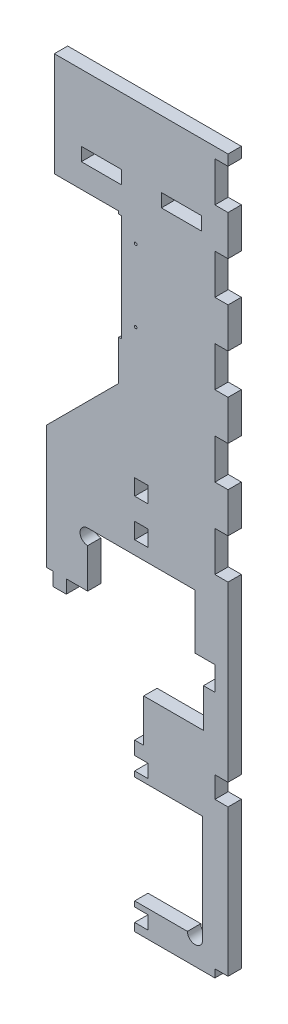
SolidWorks part; units mm, degrees
material "Balsa"
ref_plane "Plan de face" through (0, 0, 0) normal (0, 0, 1) x (1, 0, 0)
ref_plane "Plan de dessus" through (0, 0, 0) normal (0, 1, 0) x (1, 0, 0)
ref_plane "Plan de droite" through (0, 0, 0) normal (1, 0, 0) x (0, 0, -1)
sketch "Esquisse1" plane through (0, 0, 0) normal (0, 0, 1) x (1, 0, 0)
  line L0 (65.1211, 0) -> (30.1224, 0)
  line L2 (65.1211, 0) -> (65.1211, 270)
  line L3 (65.1211, 270) -> (0, 270)
  line L4 (0, 270) -> (0, 231)
  line L5 (0, 231) -> (24.1211, 231)
  line L6 (-2.8789, 101.7504) -> (12.493, 101.7504)
  line L7 (12.493, 101.7504) -> (12.493, 122.247)
  line L8 (12.493, 122.247) -> (52.693, 122.247)
  line L9 (52.693, 122.247) -> (52.693, 101.7504)
  line L10 (52.693, 101.7504) -> (55.9116, 101.7504)
  line L11 (1.3186, 101.7504) -> (30.1224, 101.7504) construction
  line L12 (55.9116, 101.7504) -> (55.9116, 78.2407)
  line L13 (55.9116, 78.2407) -> (33.5123, 78.2407)
  line L14 (33.5123, 78.2407) -> (33.5123, 62.2)
  line L15 (33.5123, 62.2) -> (30.1224, 62.2)
  line L16 (30.1224, 62.2) -> (30.1224, 57.2)
  line L17 (30.1224, 50.2) -> (55.6176, 50.2)
  line L18 (30.1224, 57.2) -> (35.1224, 57.2)
  line L19 (24.1211, 231) -> (24.1211, 175)
  line L20 (35.1224, 57.2) -> (35.1224, 52.2)
  line L21 (24.1211, 175) -> (-2.8789, 148)
  line L22 (-2.8789, 148) -> (-2.8789, 101.7504)
  line L23 (35.1224, 52.2) -> (30.1224, 52.2)
  line L24 (30.1224, 52.2) -> (30.1224, 50.2)
  line L25 (30.1224, 0) -> (30.1224, 3)
  line L26 (30.1224, 3) -> (35.1224, 3)
  line L27 (35.1224, 3) -> (35.1224, 8)
  line L30 (35.1224, 8) -> (30.1224, 8)
  line L31 (30.1224, 8) -> (30.1224, 10)
  line L32 (30.1224, 10) -> (55.6176, 10)
  line L33 (55.6176, 10) -> (55.6176, 50.2)
  dimension "D1" = 270
  dimension "D2" = 65.1211
  dimension "D3" = 40.2
  dimension "D4" = 2
  dimension "D5" = 20.4965
  dimension "D6" = 40.2
  dimension "D7" = 56
  dimension "D8" = 39
  dimension "D9" = 12.4281
  dimension "D10" = 25.4952
  dimension "D11" = 5
  dimension "D12" = 5
  dimension "D13" = 5
  dimension "D14" = 2
  dimension "D15" = 5
  dimension "D16" = 5
  dimension "D17" = 25.4952
  dimension "D18" = 135
  dimension "D19" = 41
  dimension "D20" = 68
extrude "Boss.-Extru.1" add sketch "Esquisse1" against normal blind 5
sketch "Esquisse2" plane through (0, 0, 0) normal (0, 0, 1) x (1, 0, 0)
  line L0 (52.693, 101.7504) -> (55.9116, 101.7504) construction
  line L1 (35.1224, 147.4016) -> (30.1224, 147.4016)
  line L2 (12.493, 122.247) -> (52.693, 122.247) construction
  line L3 (12.493, 101.7504) -> (12.493, 122.247) construction
  line L4 (35.1224, 147.4016) -> (35.1224, 141.4016)
  line L5 (35.1224, 141.4016) -> (30.1224, 141.4016)
  line L6 (30.1224, 147.4016) -> (30.1224, 141.4016)
  line L7 (35.1224, 133.247) -> (30.1224, 133.247)
  line L8 (35.1224, 133.247) -> (35.1224, 127.247)
  line L9 (35.1224, 127.247) -> (30.1224, 127.247)
  line L10 (30.1224, 133.247) -> (30.1224, 127.247)
  line L11 (55.9116, 101.7504) -> (60.186, 101.7504)
  line L12 (55.9116, 101.7504) -> (55.9116, 92.7704)
  line L13 (55.9116, 92.7704) -> (60.186, 92.7704)
  line L14 (60.186, 101.7504) -> (60.186, 92.7704)
  line L15 (52.693, 122.247) -> (52.693, 101.7504) construction
  line L16 (65.1211, 0) -> (65.1211, 270) construction
  line L17 (65.1211, 0) -> (60.2011, 0)
  line L18 (65.1211, 0) -> (65.1211, 3)
  line L19 (65.1211, 3) -> (60.2011, 3)
  line L20 (60.2011, 0) -> (60.2011, 3)
  line L21 (30.1224, 0) -> (65.1211, 0) construction
  line L22 (65.1211, 0) -> (65.1211, 270) construction
  line L23 (65.1211, 58) -> (60.2011, 58)
  line L24 (65.1211, 58) -> (65.1211, 66)
  line L25 (65.1211, 66) -> (60.2011, 66)
  line L26 (60.2011, 58) -> (60.2011, 66)
  line L27 (30.1224, 0) -> (65.1211, 0) construction
  line L28 (65.1211, 161) -> (60.2011, 161)
  line L29 (65.1211, 131) -> (60.2011, 131)
  line L30 (65.1211, 131) -> (65.1211, 146)
  line L31 (65.1211, 146) -> (60.2011, 146)
  line L32 (60.2011, 131) -> (60.2011, 146)
  line L33 (65.1211, 161) -> (65.1211, 176)
  line L34 (65.1211, 176) -> (60.2011, 176)
  line L35 (60.2011, 161) -> (60.2011, 176)
  line L36 (65.1211, 191) -> (60.2011, 191)
  line L37 (65.1211, 191) -> (65.1211, 206)
  line L38 (65.1211, 206) -> (60.2011, 206)
  line L39 (60.2011, 191) -> (60.2011, 206)
  line L40 (65.1211, 221) -> (60.2011, 221)
  line L41 (65.1211, 221) -> (65.1211, 236)
  line L42 (65.1211, 236) -> (60.2011, 236)
  line L43 (60.2011, 221) -> (60.2011, 236)
  line L44 (65.1211, 251) -> (60.2011, 251)
  line L45 (65.1211, 251) -> (65.1211, 266)
  line L46 (65.1211, 266) -> (60.2011, 266)
  line L47 (60.2011, 251) -> (60.2011, 266)
  line L48 (55.6176, 10) -> (30.1224, 10) construction
  line L49 (55.1211, 240) -> (40.1211, 240)
  line L50 (55.1211, 240) -> (55.1211, 245)
  line L51 (55.1211, 245) -> (40.1211, 245)
  line L52 (40.1211, 240) -> (40.1211, 245)
  line L53 (24.1211, 231) -> (24.1211, 175) construction
  line L54 (25.1211, 240) -> (10.1211, 240)
  line L55 (25.1211, 240) -> (25.1211, 245)
  line L56 (25.1211, 245) -> (10.1211, 245)
  line L57 (10.1211, 240) -> (10.1211, 245)
  line L58 (24.1211, 230) -> (25.1211, 230)
  line L59 (24.1211, 230) -> (24.1211, 190)
  line L60 (24.1211, 190) -> (25.1211, 190)
  line L61 (25.1211, 230) -> (25.1211, 190)
  line L63 (65.1211, 270) -> (0, 270) construction
  line L64 (55.6176, 50.2) -> (55.6176, 10) construction
  line L65 (0, 231) -> (24.1211, 231) construction
  circle A0 centre (12.493, 119.3895) radius 2.8575
  circle A1 centre (30.493, 223.5) radius 0.5
  circle A2 centre (30.493, 196.5) radius 0.5
  circle A3 centre (52.7601, 10) radius 2.8575
  dimension "D15" = 5.715
  dimension "D1" = 2.8575
  dimension "D2" = 7.493
  dimension "D3" = 4.92
  dimension "D4" = 3
  dimension "D5" = 4.92
  dimension "D6" = 8
  dimension "D7" = 58
  dimension "D8" = 15
  dimension "D9" = 131
  dimension "D11" = 40
  dimension "D12" = 1
  dimension "D13" = 5
  dimension "D14" = 25
  dimension "D16" = 1
  dimension "D10" = 5
extrude "Enlèv. mat.-Extru.1" cut sketch "Esquisse2" against normal blind 5
sketch "Esquisse3" plane through (0, 0, 0) normal (0, 0, 1) x (1, 0, 0)
  line L1 (4.493, 101.7504) -> (-0.507, 101.7504)
  line L2 (4.493, 101.7504) -> (4.493, 96.7504)
  line L3 (4.493, 96.7504) -> (-0.507, 96.7504)
  line L4 (-0.507, 101.7504) -> (-0.507, 96.7504)
  line L6 (-2.8789, 101.7504) -> (12.493, 101.7504) construction
  line L7 (12.493, 101.7504) -> (12.493, 116.532) construction
  dimension "D1" = 8
  dimension "D2" = 5
  dimension "D3" = 5
extrude "Boss.-Extru.2" add sketch "Esquisse3" against normal blind 5
